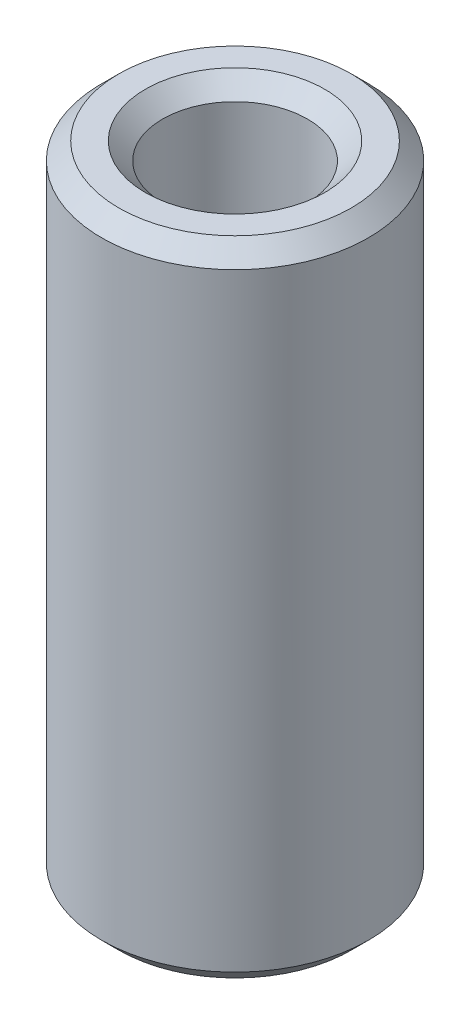
SolidWorks part; units mm, degrees
ref_plane "Front Plane" through (0, 0, 0) normal (0, 0, 1) x (1, 0, 0)
ref_plane "Top Plane" through (0, 0, 0) normal (0, 1, 0) x (1, 0, 0)
ref_plane "Right Plane" through (0, 0, 0) normal (1, 0, 0) x (0, 0, -1)
sketch "Sketch1" plane through (0, 0, 0) normal (0, 1, 0) x (1, 0, 0)
  circle A0 centre (0, 0) radius 25
  dimension "SLEEVE_OD" = 50
extrude "Boss-Extrude1" add sketch "Sketch1" along normal blind 120.4221
sketch "Sketch2" plane through (0, 0, 0) normal (0, 1, 0) x (1, 0, 0)
  circle A0 centre (0, 0) radius 13.5687
  dimension "BORE_D" = 27.1374
extrude "Cut-Extrude1" cut sketch "Sketch2" along normal through all
chamfer "Chamfer1" distance 3.2253 angle 45 4 edges at (0, 120.4221, 13.5687) (0, 0, 13.5687) (0, 0, 25) (0, 120.4221, 25)
